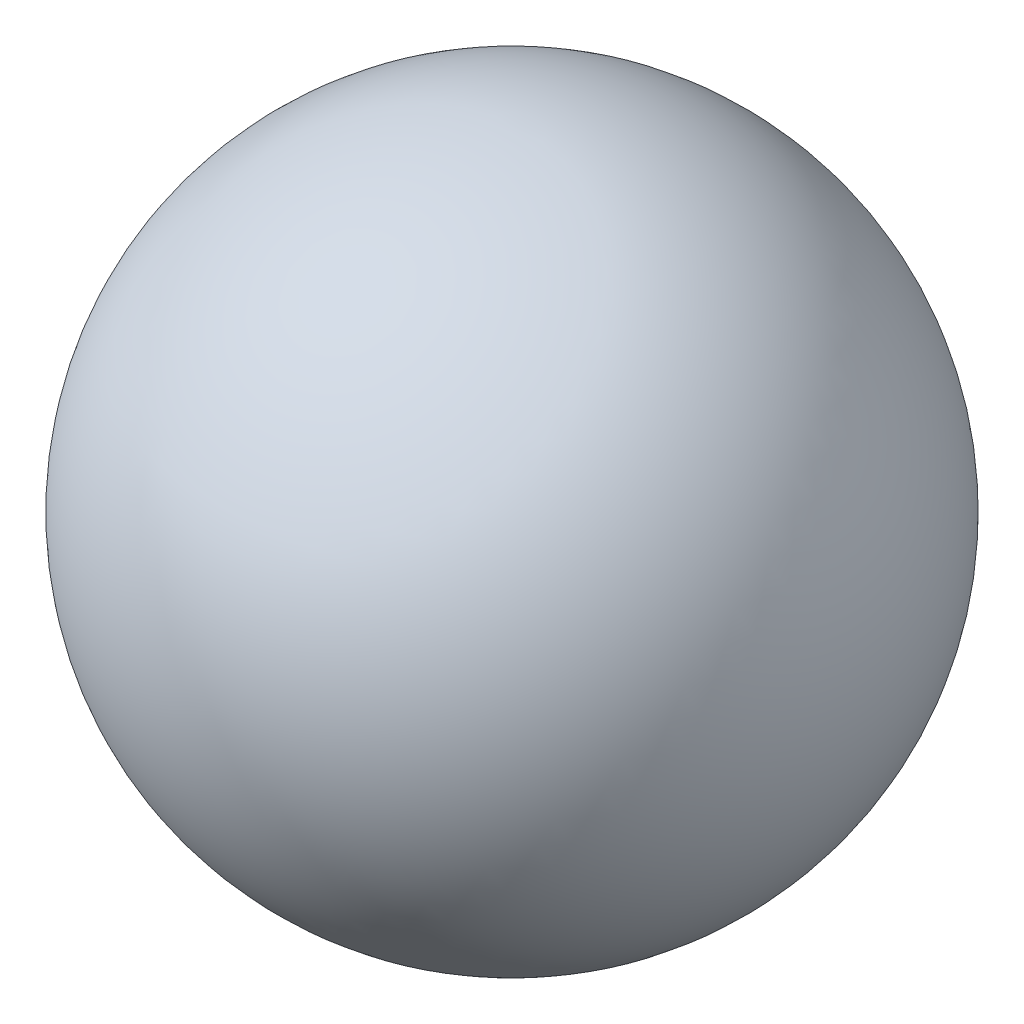
SolidWorks part; units mm, degrees
ref_plane "Front Plane" through (0, 0, 0) normal (0, 0, 1) x (1, 0, 0)
ref_plane "Top Plane" through (0, 0, 0) normal (0, 1, 0) x (1, 0, 0)
ref_plane "Right Plane" through (0, 0, 0) normal (1, 0, 0) x (0, 0, -1)
sketch "Sketch1" plane through (0, 0, 0) normal (0, 0, 1) x (1, 0, 0)
  line L0 (0, 4.5) -> (0, -4.5) construction
  line L1 (0, -4.5) -> (0, 4.5) construction
  line L2 (0, -4.5) -> (0, 4.5)
  arc A0 (0, -4.5) -> (0, 4.5) centre (0, 0) ccw
  point P6 (0, 0)
  dimension "D1" = 9
revolve "Revolve1" add sketch "Sketch1" angle 360 about L1
ref_axis "Axis1" through (4.95, 0, 0) along (-1, 0, 0)
